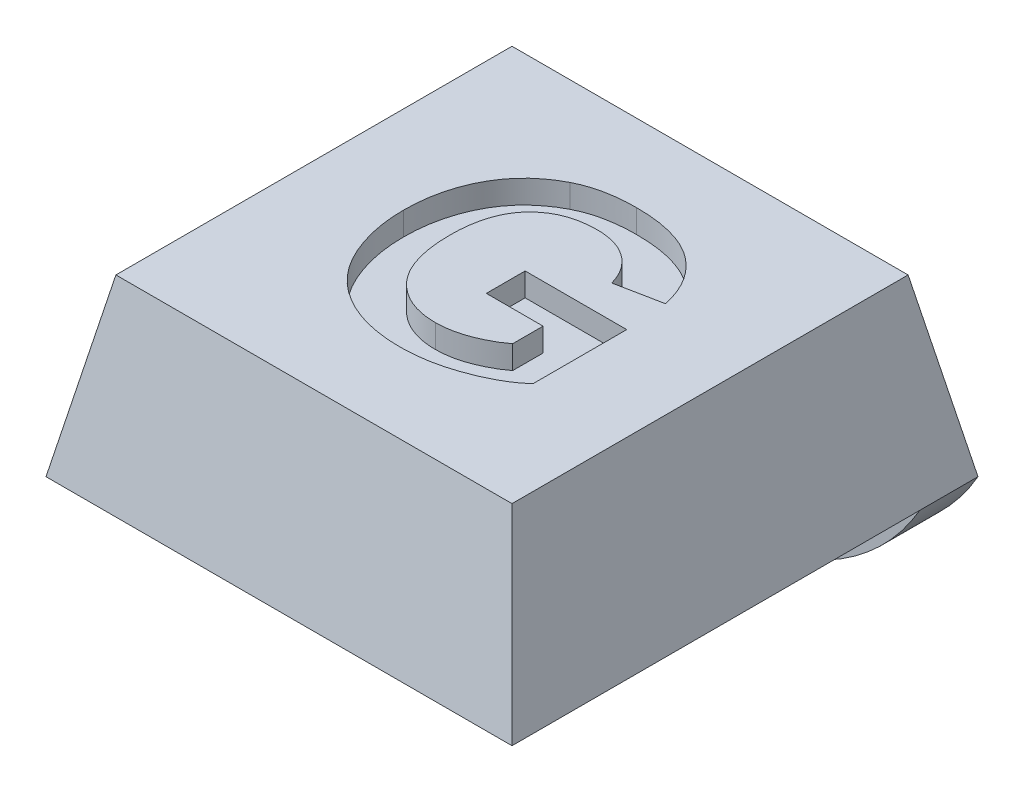
SolidWorks part; units mm, degrees
ref_plane "Front Plane" through (0, 0, 0) normal (0, 0, 1) x (1, 0, 0)
ref_plane "Top Plane" through (0, 0, 0) normal (0, 1, 0) x (1, 0, 0)
ref_plane "Right Plane" through (0, 0, 0) normal (1, 0, 0) x (0, 0, -1)
sketch "Sketch1" plane through (0, 0, 0) normal (0, 1, 0) x (1, 0, 0)
  line L1 (0, 0) -> (8, 0)
  line L2 (0, 0) -> (0, 8)
  line L3 (0, 8) -> (8, 8)
  line L4 (8, 0) -> (8, 8)
  dimension "D1" = 8
  dimension "D2" = 8
extrude "Boss-Extrude1" add sketch "Sketch1" along normal blind 3
sketch "Sketch2" plane through (0, 0, 0) normal (0, 0, 1) x (1, 0, 0)
  line L0 (0, 0) -> (0.6, 3)
  line L1 (0, 3) -> (8, 3) construction
  line L2 (0.6, 3) -> (0, 3)
  line L3 (0, 3) -> (0, 0)
  line L4 (8, 0) -> (7.4, 3)
  line L5 (7.4, 3) -> (8, 3)
  line L6 (8, 3) -> (8, 0)
  dimension "D1" = 0.6
  dimension "D2" = 0.6
extrude "Cut-Extrude1" cut sketch "Sketch2" against normal through all both and the other way through all
sketch "Sketch3" plane through (0, 0, 0) normal (1, 0, 0) x (0, 0, -1)
  line L0 (0, 0) -> (0.6, 3)
  line L1 (8, 3) -> (0, 3) construction
  line L2 (0.6, 3) -> (0, 3)
  line L3 (0, 3) -> (0, 0)
  line L4 (8, 3) -> (7.4, 3)
  line L5 (7.4, 3) -> (8, 0)
  line L6 (8, 3) -> (8, 0)
  dimension "D1" = 0.6
  dimension "D2" = 0.6
extrude "Cut-Extrude2" cut sketch "Sketch3" along normal blind 11
sketch "Sketch4" plane through (0, 0, 0) normal (0, -1, 0) x (1, 0, 0)
  line L0 (8, 0) -> (8, -8) construction
  line L3 (0, 0) -> (8, 0) construction
  circle A0 centre (4, -3.75) radius 1.8
  dimension "D1" = 3.6
  dimension "D2" = 4
  dimension "D3" = 3.75
extrude "Cut-Extrude3" cut sketch "Sketch4" against normal blind 0.8
sketch "Sketch5" plane through (0, 0, 0) normal (0, -1, 0) x (1, 0, 0)
  line L0 (8, 0) -> (8, -8) construction
  line L1 (0, -8) -> (8, -8)
  line L2 (0, -8) -> (0, -7)
  line L3 (0, -7) -> (8, -7)
  line L4 (8, -8) -> (8, -7)
  dimension "D1" = 1
extrude "Boss-Extrude2" add sketch "Sketch5" along normal blind 2
fillet "Fillet1" radius 4 2 edges at (8, -2, -7.5) (0, -2, -7.5)
sketch "Sketch6" plane through (0, 3, 0) normal (0, 1, 0) x (1, 0, 0)
  text T0 "G" font "Arial" height 4
extrude "Cut-Extrude4" cut sketch "Sketch6" against normal blind 0.4
